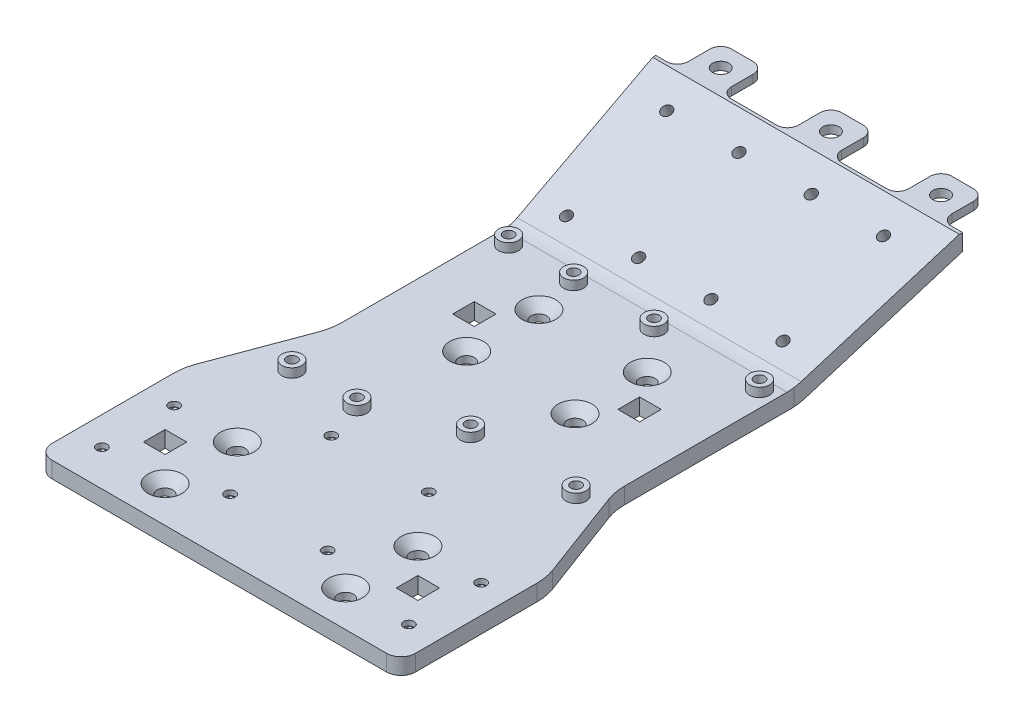
SolidWorks part; units mm, degrees
material "Onyx w/ CF"
ref_plane "Front Plane" through (0, 0, 0) normal (0, 0, 1) x (1, 0, 0)
ref_plane "Top Plane" through (0, 0, 0) normal (0, 1, 0) x (1, 0, 0)
ref_plane "Right Plane" through (0, 0, 0) normal (1, 0, 0) x (0, 0, -1)
sketch "Sketch1" plane through (0, 0, 0) normal (0, 1, 0) x (1, 0, 0)
  line L0 (-39.17, 0) -> (39.17, 0)
  line L3 (-50.325, -79.6) -> (-50.325, -120)
  line L5 (50.325, -120) -> (50.325, -79.6)
  line L8 (-50.325, -120) -> (50.325, -120)
  line L9 (39.17, 0) -> (39.17, -49.7)
  line L10 (-39.17, 0) -> (-39.17, -49.7)
  line L11 (39.17, -49.7) -> (50.325, -79.6)
  line L12 (-50.325, -79.6) -> (-39.17, -49.7)
  point P1 (0, -120)
  point P4 (0, 0)
  dimension "D1" = 78.34
  dimension "D2" = 40.4
  dimension "D3" = 120
  dimension "D4" = 49.7
  dimension "D5" = 100.65
extrude "Boss-Extrude1" add sketch "Sketch1" along normal mid plane 4.5
sketch "Sketch5" plane through (0, 2.25, 0) normal (0, 1, 0) x (1, 0, 0)
  line L3 (-22.875, -26.5) -> (22.875, -26.5) construction
  line L6 (39.17, 0) -> (-39.17, 0) construction
  line L9 (-35, -100) -> (35, -100) construction
  line L19 (-25.875, -23.5) -> (-19.875, -23.5)
  line L20 (-25.875, -23.5) -> (-25.875, -29.5)
  line L21 (-25.875, -29.5) -> (-19.875, -29.5)
  line L22 (-19.875, -23.5) -> (-19.875, -29.5)
  line L23 (-25.875, -23.5) -> (-19.875, -29.5) construction
  line L24 (-25.875, -29.5) -> (-19.875, -23.5) construction
  line L25 (19.875, -23.5) -> (25.875, -23.5)
  line L26 (19.875, -23.5) -> (19.875, -29.5)
  line L27 (19.875, -29.5) -> (25.875, -29.5)
  line L28 (25.875, -23.5) -> (25.875, -29.5)
  line L29 (19.875, -23.5) -> (25.875, -29.5) construction
  line L30 (19.875, -29.5) -> (25.875, -23.5) construction
  line L37 (-50.325, -120) -> (50.325, -120) construction
  line L44 (-38, -97) -> (-32, -97)
  line L45 (-38, -97) -> (-38, -103)
  line L46 (-38, -103) -> (-32, -103)
  line L47 (-32, -97) -> (-32, -103)
  line L48 (-38, -97) -> (-32, -103) construction
  line L49 (-38, -103) -> (-32, -97) construction
  line L50 (32, -97) -> (38, -97)
  line L51 (32, -97) -> (32, -103)
  line L52 (32, -103) -> (38, -103)
  line L53 (38, -97) -> (38, -103)
  line L54 (32, -97) -> (38, -103) construction
  line L55 (32, -103) -> (38, -97) construction
  point P4 (0, -26.5)
  point P5 (0, -100)
  dimension "D1" = 26.5
  dimension "D2" = 45.75
  dimension "D3" = 6
  dimension "D4" = 70
  dimension "D7" = 20
extrude "Cut-Extrude1" cut sketch "Sketch5" against normal through all
hole_wizard "CSK for M4 Flat Head Machine Screw1" positions "Sketch6" profile "Sketch7" countersink size "M4" standard "ANSI Metric" end condition through all
sketch "Sketch6" plane through (0, 2.25, 0) normal (0, -1, 0) x (-1, 0, 0)
  line L1 (-15, -16.5) -> (15, -16.5)
  line L2 (-15, -16.5) -> (-15, -36.5)
  line L3 (-15, -36.5) -> (15, -36.5)
  line L4 (15, -16.5) -> (15, -36.5)
  line L5 (-15, -16.5) -> (15, -36.5) construction
  line L6 (-15, -36.5) -> (15, -16.5) construction
  line L7 (-39.17, 0) -> (39.17, 0) construction
  line L9 (-25, -90) -> (25, -90)
  line L10 (-25, -90) -> (-25, -110)
  line L11 (-25, -110) -> (25, -110)
  line L12 (25, -90) -> (25, -110)
  line L13 (-25, -90) -> (25, -110) construction
  line L14 (-25, -110) -> (25, -90) construction
  line L15 (50.325, -120) -> (-50.325, -120) construction
  point P0 (-15, -16.5)
  point P3 (15, -16.5)
  point P6 (15, -36.5)
  point P8 (-15, -36.5)
  point P49 (0, -36.5)
  point P66 (25, -110)
  point P69 (-25, -90)
  point P70 (-25, -110)
  point P71 (25, -90)
  point P96 (0, -90)
  dimension "D1" = 16.5
  dimension "D2" = 20
  dimension "D3" = 30
  dimension "D4" = 20
  dimension "D5" = 50
  dimension "D6" = 10
sketch "Sketch7" plane through (15, 2.25, 16.5) normal (1, 0, 0) x (0, 0, 1)
  line L0 (0, 0) -> (0, 4.5)
  line L1 (0, 4.5) -> (2.15, 4.5)
  line L2 (2.15, 4.5) -> (2.15, 2.55)
  line L3 (2.15, 2.55) -> (4.7, 0)
  line L5 (4.7, 0) -> (0, 0)
  line L6 (-2.15, 2.55) -> (-4.7, 0) construction
  line L11 (0, -6.35) -> (0, 107.95) construction
  dimension "Thru Hole Dia." = 4.3
  dimension "Thru Hole Depth" = 4.5
  dimension "Near C'Sink Dia." = 9.4
  dimension "Near C'Sink Angle" = 90
fillet "Fillet2" radius 4 2 edges at (-50.325, 0, 120) (50.325, 0, 120)
fillet "Fillet3" radius 15 4 edges at (50.325, 0, 79.6) (39.17, 0, 49.7) (-50.325, 0, 79.6) (-39.17, 0, 49.7)
sketch "Sketch18" plane through (0, 0, 0) normal (1, 0, 0) x (0, 0, -1)
  line L0 (0, 2.25) -> (42.4584, 19.55)
  line L1 (42.4584, 19.55) -> (43.34, 19.55)
  line L2 (43.34, 19.55) -> (43.34, 15.05)
  line L3 (43.34, 15.05) -> (0.8816, -2.25)
  line L4 (0.8816, -2.25) -> (0, -2.25)
  line L5 (0, 2.25) -> (0, -2.25) construction
  line L6 (0, 2.25) -> (0, -2.25)
  dimension "D1" = 43.34
  dimension "D2" = 17.3
  dimension "D3" = 4.5
extrude "Boss-Extrude2" add sketch "Sketch18" against normal mid plane 85
sketch "Sketch21" plane through (0, -2.25, 0) normal (0, -1, 0) x (1, 0, 0)
  line L0 (39.17, 0) -> (42.5, -43.34)
  line L1 (42.5, -43.34) -> (42.5, 0)
  line L2 (42.5, 0) -> (39.17, 0)
  line L3 (39.17, 0) -> (42.5, 0) construction
  line L4 (0, -11.99) -> (0, 11.99) construction
  line L5 (-42.5, 0) -> (-39.17, 0)
  line L6 (-42.5, -43.34) -> (-42.5, 0)
  line L7 (-39.17, 0) -> (-42.5, -43.34)
extrude "Cut-Extrude5" cut sketch "Sketch21" against normal through all
fillet "Fillet5" radius 10 2 edges at (0, 2.25, 0) (0, -2.25, -0.8816)
sketch "Sketch22" plane through (0, 19.55, 0) normal (0, 1, 0) x (1, 0, 0)
  line L0 (-42.5, 43.34) -> (42.5, 43.34) construction
  line L1 (-36.5, 43.34) -> (-24.5, 43.34)
  line L2 (-36.5, 43.34) -> (-36.5, 55.34)
  line L3 (-36.5, 55.34) -> (-24.5, 55.34)
  line L4 (-24.5, 43.34) -> (-24.5, 55.34)
  line L5 (-32.5, 49.34) -> (-36.5, 49.34) construction
  line L6 (6, 43.34) -> (-6, 43.34)
  line L7 (6, 43.34) -> (6, 55.34)
  line L8 (6, 55.34) -> (-6, 55.34)
  line L9 (-6, 43.34) -> (-6, 55.34)
  line L10 (6, 43.34) -> (-6, 55.34) construction
  line L11 (6, 55.34) -> (-6, 43.34) construction
  line L12 (-30.5, 51.34) -> (-30.5, 55.34) construction
  line L13 (0, -11.99) -> (0, 11.99) construction
  line L14 (36.5, 55.34) -> (24.5, 55.34)
  line L15 (24.5, 43.34) -> (24.5, 55.34)
  line L16 (36.5, 43.34) -> (24.5, 43.34)
  line L17 (36.5, 43.34) -> (36.5, 55.34)
  circle A0 centre (-30.5, 49.34) radius 2 construction
  point P6 (0, 49.34)
  point P11 (0, 43.34)
  point P12 (-30.5, 55.34)
  point P17 (-24.5, 49.34)
  dimension "D2" = 4
  dimension "D1" = 12
  dimension "D3" = 4
extrude "Boss-Extrude3" add sketch "Sketch22" against normal blind 2.25
fillet "Fillet6" radius 3 12 edges at (-36.5, 18.425, -55.34) (-36.5, 18.425, -43.34) (-24.5, 18.425, -55.34) (-24.5, 18.425, -43.34) (-6, 18.425, -43.34) (-6, 18.425, -55.34) (6, 18.425, -55.34) (6, 18.425, -43.34) (24.5, 18.425, -43.34) (36.5, 18.425, -43.34) (36.5, 18.425, -55.34) (24.5, 18.425, -55.34)
hole_wizard "M4 Clearance Hole1" positions "Sketch23" profile "Sketch24" hole size "M4" standard "ANSI Metric" end condition through all
sketch "Sketch23" plane through (0, 19.55, 0) normal (0, 1, 0) x (1, 0, 0)
  line L0 (-27.5, 55.34) -> (-33.5, 55.34) construction
  line L1 (-24.5, 46.34) -> (-24.5, 52.34) construction
  line L2 (33.5, 55.34) -> (27.5, 55.34) construction
  line L3 (3, 55.34) -> (-3, 55.34) construction
  point P0 (30.5, 49.34)
  point P2 (0, 49.34)
  point P4 (-30.5, 49.34)
  point P9 (-30.5, 55.34)
  point P12 (-24.5, 49.34)
  point P17 (30.5, 55.34)
  point P20 (0, 55.34)
sketch "Sketch24" plane through (30.5, 19.55, -49.34) normal (1, 0, 0) x (0, 0, 1)
  line L0 (0, 0) -> (0, 21.8)
  line L1 (0, 21.8) -> (2.25, 21.8)
  line L2 (2.25, 21.8) -> (2.25, 0)
  line L5 (2.25, 0) -> (0, 0)
  line L11 (0, -6.35) -> (0, 107.95) construction
  dimension "Thru Hole Dia." = 4.5
  dimension "Thru Hole Depth" = 21.8
hole_wizard "M2.5 Clearance Hole2" positions "Sketch29" profile "Sketch30" hole size "M2.5" standard "ANSI Metric" end condition through all
sketch "Sketch29" plane through (0, 1.9296, 0.7862) normal (0, 0.9261, 0.3773) x (1, 0, 0)
  line L3 (0, 46.6967) -> (0, 0) construction
  line L4 (-42.4323, 46.6967) -> (42.4323, 46.6967) construction
  line L6 (9.17, 38.3483) -> (9.17, 8.3483) construction
  point P0 (29.17, 38.3483)
  point P2 (9.17, 38.3483)
  point P4 (-10.83, 38.3483)
  point P6 (-30.83, 38.3483)
  point P11 (29.17, 8.3483)
  point P13 (9.17, 8.3483)
  point P15 (-10.83, 8.3483)
  point P17 (-30.83, 8.3483)
  point P42 (0, 23.3483)
  point P43 (9.17, 23.3483)
  dimension "D1" = 10
  dimension "D2" = 20
  dimension "D3" = 20
  dimension "D4" = 20
  dimension "D5" = 30
sketch "Sketch30" plane through (29.17, 16.3999, -34.7272) normal (1, 0, 0) x (0, -0.3773, 0.9261)
  line L0 (0, 0) -> (0, 25.0492)
  line L1 (0, 25.0492) -> (1.45, 25.0492)
  line L2 (1.45, 25.0492) -> (1.45, 0)
  line L5 (1.45, 0) -> (0, 0)
  line L11 (0, -6.35) -> (0, 107.95) construction
  dimension "Thru Hole Dia." = 2.9
  dimension "Thru Hole Depth" = 25.0492
sketch "Sketch31" plane through (0, 2.25, 0) normal (0, 1, 0) x (1, 0, 0)
  line L0 (39.17, -1.9591) -> (-39.17, -1.9591) construction
  line L1 (1.07, -1.9591) -> (39.17, -1.9591) construction
  line L2 (1.07, -1.9591) -> (1.07, -59.1091) construction
  line L3 (1.07, -59.1091) -> (39.17, -59.1091) construction
  line L4 (39.17, -1.9591) -> (39.17, -59.1091) construction
  line L5 (39.17, -46.993) -> (39.17, -1.9591) construction
  line L6 (34.725, -5.1341) -> (5.515, -5.1341) construction
  line L7 (34.725, -5.1341) -> (34.725, -55.9341) construction
  line L9 (-16.67, -5.2091) -> (-16.67, -65.2091) construction
  line L10 (-16.67, -65.2091) -> (-34.67, -65.2091) construction
  line L11 (-34.67, -65.2091) -> (-34.67, -5.2091) construction
  line L12 (-34.67, -5.2091) -> (-16.67, -5.2091) construction
  line L13 (-39.17, -1.9591) -> (-39.17, -46.993) construction
  circle A0 centre (34.725, -5.1341) radius 2.75
  circle A1 centre (5.515, -5.1341) radius 2.75
  circle A2 centre (5.515, -55.9341) radius 2.75
  circle A3 centre (34.725, -55.9341) radius 2.75
  circle A4 centre (34.725, -5.1341) radius 1.25 construction
  circle A5 centre (-16.67, -5.2091) radius 2.75
  circle A6 centre (-34.67, -5.2091) radius 2.75
  circle A7 centre (-34.67, -65.2091) radius 2.75
  circle A8 centre (-16.67, -65.2091) radius 2.75
  point P16 (20.12, -1.9591)
  point P17 (20.12, -5.1341)
  point P18 (34.725, -30.5341)
  point P19 (39.17, -30.5341)
  dimension "D3" = 3.175
  dimension "D5" = 2.5
  dimension "D6" = 5.5
  dimension "D7" = 4.5
  dimension "D11" = 5.5
  dimension "D1" = 38.1
  dimension "D2" = 57.15
  dimension "D4" = 29.21
  dimension "D8" = 3.25
  dimension "D9" = 60
  dimension "D10" = 18
extrude "Boss-Extrude4" add sketch "Sketch31" along normal blind 2.5
hole_wizard "M2.5 Clearance Hole3" positions "Sketch32" profile "Sketch33" hole size "M2.5" standard "ANSI Metric" end condition through all
sketch "Sketch32" plane through (0, 4.75, 0) normal (0, 1, 0) x (1, 0, 0)
  line L1 (13.5, -75.5) -> (-13.5, -75.5)
  line L2 (13.5, -75.5) -> (13.5, -103.5)
  line L3 (13.5, -103.5) -> (-13.5, -103.5)
  line L4 (-13.5, -75.5) -> (-13.5, -103.5)
  line L5 (-46.325, -120) -> (46.325, -120) construction
  line L6 (42.5, -90) -> (42.5, -110)
  line L8 (-42.5, -90) -> (-42.5, -110)
  line L10 (42.5, -100) -> (-42.5, -100) construction
  circle A0 centre (34.725, -5.1341) radius 2.75 construction
  circle A1 centre (34.725, -55.9341) radius 2.75 construction
  circle A2 centre (5.515, -5.1341) radius 2.75 construction
  circle A3 centre (5.515, -55.9341) radius 2.75 construction
  circle A4 centre (-16.67, -5.2091) radius 2.75 construction
  circle A5 centre (-16.67, -65.2091) radius 2.75 construction
  circle A6 centre (-34.67, -5.2091) radius 2.75 construction
  circle A7 centre (-34.67, -65.2091) radius 2.75 construction
  point P0 (34.725, -5.1341)
  point P2 (34.725, -55.9341)
  point P4 (5.515, -55.9341)
  point P6 (5.515, -5.1341)
  point P8 (-16.67, -5.2091)
  point P10 (-16.67, -65.2091)
  point P12 (-34.67, -65.2091)
  point P14 (-34.67, -5.2091)
  point P42 (13.5, -75.5)
  point P43 (-13.5, -103.5)
  point P46 (13.5, -103.5)
  point P47 (-13.5, -75.5)
  point P71 (0, -75.5)
  point P88 (-42.5, -90)
  point P90 (-42.5, -110)
  point P92 (42.5, -90)
  point P94 (42.5, -110)
  point P109 (0, -100)
  point P110 (0, -103.5)
  dimension "D1" = 16.5
  dimension "D2" = 28
  dimension "D3" = 27
  dimension "D4" = 85
  dimension "D5" = 20
  dimension "D6" = 20
sketch "Sketch33" plane through (34.725, 4.75, 5.1341) normal (1, 0, 0) x (0, 0, 1)
  line L0 (0, 0) -> (0, 7)
  line L1 (0, 7) -> (1.45, 7)
  line L2 (1.45, 7) -> (1.45, 0)
  line L5 (1.45, 0) -> (0, 0)
  line L11 (0, -6.35) -> (0, 107.95) construction
  dimension "Thru Hole Dia." = 2.9
  dimension "Thru Hole Depth" = 7
sketch "Sketch34" plane through (0, 0, 0) normal (0, 1, 0) x (1, 0, 0)
  line L0 (37.3024, -2.2567) -> (37.3024, -8.0115)
  line L1 (7.94, -2.4091) -> (3.09, -2.4091) construction
  line L2 (7.94, -2.4091) -> (7.94, -7.8591) construction
  line L3 (7.94, -7.8591) -> (3.09, -7.8591) construction
  line L4 (3.09, -2.4091) -> (3.09, -7.8591) construction
  line L5 (7.94, -2.4091) -> (3.09, -7.8591) construction
  line L6 (7.94, -7.8591) -> (3.09, -2.4091) construction
  line L7 (7.94, -53.2091) -> (3.09, -53.2091) construction
  line L8 (7.94, -53.2091) -> (7.94, -58.6591) construction
  line L9 (7.94, -58.6591) -> (3.09, -58.6591) construction
  line L10 (3.09, -53.2091) -> (3.09, -58.6591) construction
  line L11 (7.94, -53.2091) -> (3.09, -58.6591) construction
  line L12 (7.94, -58.6591) -> (3.09, -53.2091) construction
  line L13 (37.15, -53.2091) -> (32.3, -53.2091) construction
  line L14 (37.15, -53.2091) -> (37.15, -58.6591) construction
  line L15 (37.15, -58.6591) -> (32.3, -58.6591) construction
  line L16 (32.3, -53.2091) -> (32.3, -58.6591) construction
  line L17 (37.15, -53.2091) -> (32.3, -58.6591) construction
  line L18 (37.15, -58.6591) -> (32.3, -53.2091) construction
  line L19 (37.15, -2.4091) -> (32.3, -2.4091) construction
  line L20 (37.15, -2.4091) -> (37.15, -7.8591) construction
  line L21 (37.15, -7.8591) -> (32.3, -7.8591) construction
  line L22 (32.3, -2.4091) -> (32.3, -7.8591) construction
  line L23 (37.15, -2.4091) -> (32.3, -7.8591) construction
  line L24 (37.15, -7.8591) -> (32.3, -2.4091) construction
  line L25 (-14.245, -2.4841) -> (-19.095, -2.4841) construction
  line L26 (-14.245, -2.4841) -> (-14.245, -7.9341) construction
  line L27 (-14.245, -7.9341) -> (-19.095, -7.9341) construction
  line L28 (-19.095, -2.4841) -> (-19.095, -7.9341) construction
  line L29 (-14.245, -2.4841) -> (-19.095, -7.9341) construction
  line L30 (-14.245, -7.9341) -> (-19.095, -2.4841) construction
  line L31 (-32.245, -2.4841) -> (-37.095, -2.4841) construction
  line L32 (-32.245, -2.4841) -> (-32.245, -7.9341) construction
  line L33 (-32.245, -7.9341) -> (-37.095, -7.9341) construction
  line L34 (-37.095, -2.4841) -> (-37.095, -7.9341) construction
  line L35 (-32.245, -2.4841) -> (-37.095, -7.9341) construction
  line L36 (-32.245, -7.9341) -> (-37.095, -2.4841) construction
  line L37 (-32.245, -62.4841) -> (-37.095, -62.4841) construction
  line L38 (-32.245, -62.4841) -> (-32.245, -67.9341) construction
  line L39 (-32.245, -67.9341) -> (-37.095, -67.9341) construction
  line L40 (-37.095, -62.4841) -> (-37.095, -67.9341) construction
  line L41 (-32.245, -62.4841) -> (-37.095, -67.9341) construction
  line L42 (-32.245, -67.9341) -> (-37.095, -62.4841) construction
  line L43 (-14.245, -62.4841) -> (-19.095, -62.4841) construction
  line L44 (-14.245, -62.4841) -> (-14.245, -67.9341) construction
  line L45 (-14.245, -67.9341) -> (-19.095, -67.9341) construction
  line L46 (-19.095, -62.4841) -> (-19.095, -67.9341) construction
  line L47 (-14.245, -62.4841) -> (-19.095, -67.9341) construction
  line L48 (-14.245, -67.9341) -> (-19.095, -62.4841) construction
  line L49 (37.3024, -8.0115) -> (32.1476, -8.0115)
  line L50 (32.1476, -2.2567) -> (32.1476, -8.0115)
  line L51 (37.3024, -2.2567) -> (32.1476, -2.2567)
  line L52 (32.1476, -53.0567) -> (32.1476, -58.8115)
  line L53 (37.3024, -58.8115) -> (32.1476, -58.8115)
  line L54 (37.3024, -53.0567) -> (37.3024, -58.8115)
  line L55 (37.3024, -53.0567) -> (32.1476, -53.0567)
  line L56 (2.9376, -53.0567) -> (2.9376, -58.8115)
  line L57 (8.0924, -58.8115) -> (2.9376, -58.8115)
  line L58 (8.0924, -53.0567) -> (8.0924, -58.8115)
  line L59 (8.0924, -53.0567) -> (2.9376, -53.0567)
  line L60 (2.9376, -2.2567) -> (2.9376, -8.0115)
  line L61 (8.0924, -8.0115) -> (2.9376, -8.0115)
  line L62 (8.0924, -2.2567) -> (8.0924, -8.0115)
  line L63 (8.0924, -2.2567) -> (2.9376, -2.2567)
  line L64 (-19.2474, -2.3317) -> (-19.2474, -8.0865)
  line L65 (-14.0926, -8.0865) -> (-19.2474, -8.0865)
  line L66 (-14.0926, -2.3317) -> (-14.0926, -8.0865)
  line L67 (-14.0926, -2.3317) -> (-19.2474, -2.3317)
  line L68 (-32.0926, -2.3317) -> (-32.0926, -8.0865)
  line L69 (-32.0926, -8.0865) -> (-37.2474, -8.0865)
  line L70 (-37.2474, -2.3317) -> (-37.2474, -8.0865)
  line L71 (-32.0926, -2.3317) -> (-37.2474, -2.3317)
  line L72 (-19.2474, -62.3317) -> (-19.2474, -68.0865)
  line L73 (-14.0926, -68.0865) -> (-19.2474, -68.0865)
  line L74 (-14.0926, -62.3317) -> (-14.0926, -68.0865)
  line L75 (-14.0926, -62.3317) -> (-19.2474, -62.3317)
  line L76 (-32.0926, -62.3317) -> (-32.0926, -68.0865)
  line L77 (-32.0926, -68.0865) -> (-37.2474, -68.0865)
  line L78 (-37.2474, -62.3317) -> (-37.2474, -68.0865)
  line L79 (-32.0926, -62.3317) -> (-37.2474, -62.3317)
  line L80 (16.0774, -78.3774) -> (10.9226, -78.3774)
  line L81 (15.925, -72.775) -> (11.075, -72.775) construction
  line L82 (15.925, -72.775) -> (15.925, -78.225) construction
  line L83 (15.925, -78.225) -> (11.075, -78.225) construction
  line L84 (11.075, -72.775) -> (11.075, -78.225) construction
  line L85 (15.925, -72.775) -> (11.075, -78.225) construction
  line L86 (15.925, -78.225) -> (11.075, -72.775) construction
  line L87 (15.925, -100.775) -> (11.075, -100.775) construction
  line L88 (15.925, -100.775) -> (15.925, -106.225) construction
  line L89 (15.925, -106.225) -> (11.075, -106.225) construction
  line L90 (11.075, -100.775) -> (11.075, -106.225) construction
  line L91 (15.925, -100.775) -> (11.075, -106.225) construction
  line L92 (15.925, -106.225) -> (11.075, -100.775) construction
  line L93 (-11.075, -100.775) -> (-15.925, -100.775) construction
  line L94 (-11.075, -100.775) -> (-11.075, -106.225) construction
  line L95 (-11.075, -106.225) -> (-15.925, -106.225) construction
  line L96 (-15.925, -100.775) -> (-15.925, -106.225) construction
  line L97 (-11.075, -100.775) -> (-15.925, -106.225) construction
  line L98 (-11.075, -106.225) -> (-15.925, -100.775) construction
  line L99 (-11.075, -72.775) -> (-15.925, -72.775) construction
  line L100 (-11.075, -72.775) -> (-11.075, -78.225) construction
  line L101 (-11.075, -78.225) -> (-15.925, -78.225) construction
  line L102 (-15.925, -72.775) -> (-15.925, -78.225) construction
  line L103 (-11.075, -72.775) -> (-15.925, -78.225) construction
  line L104 (-11.075, -78.225) -> (-15.925, -72.775) construction
  line L105 (10.9226, -72.6226) -> (10.9226, -78.3774)
  line L106 (16.0774, -72.6226) -> (10.9226, -72.6226)
  line L107 (16.0774, -72.6226) -> (16.0774, -78.3774)
  line L108 (16.0774, -100.6226) -> (10.9226, -100.6226)
  line L109 (10.9226, -100.6226) -> (10.9226, -106.3774)
  line L110 (16.0774, -106.3774) -> (10.9226, -106.3774)
  line L111 (16.0774, -100.6226) -> (16.0774, -106.3774)
  line L112 (-10.9226, -78.3774) -> (-16.0774, -78.3774)
  line L113 (-16.0774, -72.6226) -> (-16.0774, -78.3774)
  line L114 (-10.9226, -72.6226) -> (-16.0774, -72.6226)
  line L115 (-10.9226, -72.6226) -> (-10.9226, -78.3774)
  line L116 (-10.9226, -100.6226) -> (-16.0774, -100.6226)
  line L117 (-16.0774, -100.6226) -> (-16.0774, -106.3774)
  line L118 (-10.9226, -106.3774) -> (-16.0774, -106.3774)
  line L119 (-10.9226, -100.6226) -> (-10.9226, -106.3774)
  line L120 (39.9226, -87.1226) -> (39.9226, -92.8774)
  line L121 (44.925, -87.275) -> (40.075, -87.275) construction
  line L122 (44.925, -87.275) -> (44.925, -92.725) construction
  line L123 (44.925, -92.725) -> (40.075, -92.725) construction
  line L124 (40.075, -87.275) -> (40.075, -92.725) construction
  line L125 (44.925, -87.275) -> (40.075, -92.725) construction
  line L126 (44.925, -92.725) -> (40.075, -87.275) construction
  line L127 (44.925, -107.275) -> (40.075, -107.275) construction
  line L128 (44.925, -107.275) -> (44.925, -112.725) construction
  line L129 (44.925, -112.725) -> (40.075, -112.725) construction
  line L130 (40.075, -107.275) -> (40.075, -112.725) construction
  line L131 (44.925, -107.275) -> (40.075, -112.725) construction
  line L132 (44.925, -112.725) -> (40.075, -107.275) construction
  line L133 (-40.075, -87.275) -> (-44.925, -87.275) construction
  line L134 (-40.075, -87.275) -> (-40.075, -92.725) construction
  line L135 (-40.075, -92.725) -> (-44.925, -92.725) construction
  line L136 (-44.925, -87.275) -> (-44.925, -92.725) construction
  line L137 (-40.075, -87.275) -> (-44.925, -92.725) construction
  line L138 (-40.075, -92.725) -> (-44.925, -87.275) construction
  line L139 (-40.075, -107.275) -> (-44.925, -107.275) construction
  line L140 (-40.075, -107.275) -> (-40.075, -112.725) construction
  line L141 (-40.075, -112.725) -> (-44.925, -112.725) construction
  line L142 (-44.925, -107.275) -> (-44.925, -112.725) construction
  line L143 (-40.075, -107.275) -> (-44.925, -112.725) construction
  line L144 (-40.075, -112.725) -> (-44.925, -107.275) construction
  line L145 (45.0774, -92.8774) -> (39.9226, -92.8774)
  line L146 (45.0774, -87.1226) -> (45.0774, -92.8774)
  line L147 (45.0774, -87.1226) -> (39.9226, -87.1226)
  line L148 (45.0774, -107.1226) -> (39.9226, -107.1226)
  line L149 (39.9226, -107.1226) -> (39.9226, -112.8774)
  line L150 (45.0774, -112.8774) -> (39.9226, -112.8774)
  line L151 (45.0774, -107.1226) -> (45.0774, -112.8774)
  line L152 (-45.0774, -87.1226) -> (-45.0774, -92.8774)
  line L153 (-39.9226, -92.8774) -> (-45.0774, -92.8774)
  line L154 (-39.9226, -87.1226) -> (-39.9226, -92.8774)
  line L155 (-39.9226, -87.1226) -> (-45.0774, -87.1226)
  line L156 (-39.9226, -107.1226) -> (-45.0774, -107.1226)
  line L157 (-45.0774, -107.1226) -> (-45.0774, -112.8774)
  line L158 (-39.9226, -112.8774) -> (-45.0774, -112.8774)
  line L159 (-39.9226, -107.1226) -> (-39.9226, -112.8774)
  circle A0 centre (34.725, -5.1341) radius 1.45 construction
  circle A1 centre (34.725, -55.9341) radius 2.75 construction
  circle A2 centre (5.515, -5.1341) radius 2.75 construction
  circle A3 centre (5.515, -55.9341) radius 2.75 construction
  circle A4 centre (-16.67, -5.2091) radius 2.75 construction
  circle A5 centre (-16.67, -65.2091) radius 2.75 construction
  circle A6 centre (-34.67, -5.2091) radius 2.75 construction
  circle A7 centre (-34.67, -65.2091) radius 2.75 construction
  circle A8 centre (-13.5, -75.5) radius 1.45 construction
  circle A9 centre (13.5, -75.5) radius 1.45 construction
  circle A10 centre (13.5, -103.5) radius 1.45 construction
  circle A11 centre (-13.5, -103.5) radius 1.45 construction
  circle A13 centre (-42.5, -90) radius 1.45 construction
  circle A14 centre (-42.5, -110) radius 1.45 construction
  circle A15 centre (42.5, -90) radius 1.45 construction
  circle A16 centre (42.5, -110) radius 1.45 construction
  point P0 (5.515, -5.1341)
  point P5 (5.515, -55.9341)
  point P10 (34.725, -55.9341)
  point P15 (34.725, -5.1341)
  point P20 (-16.67, -5.2091)
  point P25 (-34.67, -5.2091)
  point P30 (-34.67, -65.2091)
  point P35 (-16.67, -65.2091)
  point P42 (13.5, -103.5)
  point P55 (-13.5, -103.5)
  point P98 (13.5, -75.5)
  point P103 (-13.5, -75.5)
  point P110 (42.5, -90)
  point P121 (42.5, -110)
  point P142 (-42.5, -90)
  point P147 (-42.5, -110)
  point P154 (8.3674, -53.0817)
  point P155 (-14.0926, -2.8648)
  point P158 (0, 0)
  point P161 (0, 0)
  dimension "D1" = 5.45
  dimension "D2" = 0.1524
  dimension "D3" = 0.1524
  dimension "D4" = 0.1524
  dimension "D5" = 4.85
extrude "Cut-Extrude6" cut sketch "Sketch34" against normal mid plane 1.7
